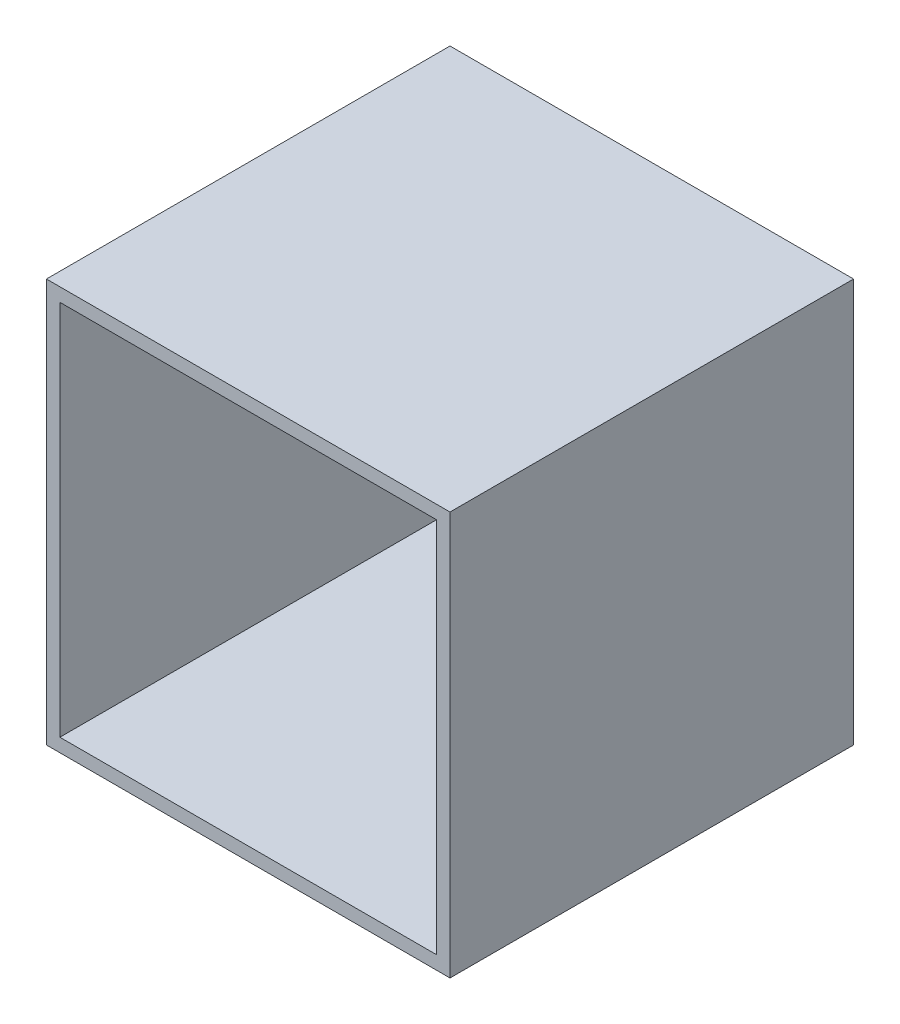
SolidWorks part; units mm, degrees
ref_plane "Front Plane" through (0, 0, 0) normal (0, 0, 1) x (1, 0, 0)
ref_plane "Top Plane" through (0, 0, 0) normal (0, 1, 0) x (1, 0, 0)
ref_plane "Right Plane" through (0, 0, 0) normal (1, 0, 0) x (0, 0, -1)
sketch "Sketch1" plane through (0, 0, 0) normal (0, 1, 0) x (1, 0, 0)
  line L1 (-38.1, -38.1) -> (38.1, -38.1)
  line L2 (-38.1, -38.1) -> (-38.1, 38.1)
  line L3 (-38.1, 38.1) -> (38.1, 38.1)
  line L4 (38.1, -38.1) -> (38.1, 38.1)
  line L5 (-38.1, -38.1) -> (38.1, 38.1) construction
  line L6 (-38.1, 38.1) -> (38.1, -38.1) construction
  point P0 (0, 0)
  dimension "D1" = 76.2
  dimension "D2" = 76.2
extrude "box" add sketch "Sketch1" along normal blind 76.2
shell "hollow it" thickness 2.54 removed face at (0, 38.1, 38.1)
sketch "Sketch2" plane through (0, 0, -38.1) normal (0, 0, -1) x (-1, 0, 0)
  line L0 (-38.1, 76.2) -> (38.1, 76.2) construction
  line L1 (-31.75, 69.85) -> (-24.13, 69.85)
  line L2 (-31.75, 69.85) -> (-31.75, 6.35)
  line L3 (-31.75, 6.35) -> (-24.13, 6.35)
  line L4 (-24.13, 69.85) -> (-24.13, 6.35)
  line L6 (-38.1, 76.2) -> (-38.1, 0) construction
  dimension "D1" = 7.62
  dimension "D2" = 63.5
  dimension "D3" = 6.35
  dimension "D4" = 6.35
extrude "slider track" cut sketch "Sketch2" against normal up to surface (2.54 mm away) up to face at (0, 38.1, -35.56)
sketch "Sketch4" plane through (0, 0, -38.1) normal (0, 0, -1) x (-1, 0, 0)
  line L0 (-38.1, 76.2) -> (38.1, 76.2) construction
  circle A0 centre (0, 63.5) radius 6.35
  dimension "D1" = 12.7
  dimension "D2" = 12.7
extrude "button large ring" cut sketch "Sketch4" against normal blind 1.27
sketch "Sketch5" plane through (0, 0, -36.83) normal (0, 0, -1) x (-1, 0, 0)
  circle A0 centre (0, 63.5) radius 3.556
  circle A1 centre (0, 63.5) radius 6.35 construction
  dimension "D2" = 7.112
  dimension "D1" = 0
extrude "button small hole" cut sketch "Sketch5" against normal blind 1.27
sketch "Sketch6" plane through (0, 0, -38.1) normal (0, 0, -1) x (-1, 0, 0)
  line L0 (-3.2977, 45.72) -> (-3.2977, 52.07)
  line L1 (-3.2977, 52.07) -> (3.0523, 52.07)
  line L2 (3.0523, 52.07) -> (3.0523, 45.72)
  line L3 (3.0523, 45.72) -> (9.4023, 45.72)
  line L4 (9.4023, 45.72) -> (9.4023, 39.37)
  line L5 (9.4023, 39.37) -> (3.0523, 39.37)
  line L6 (3.0523, 39.37) -> (3.0523, 33.02)
  line L7 (3.0523, 33.02) -> (-3.2977, 33.02)
  line L8 (-3.2977, 33.02) -> (-3.2977, 39.37)
  line L9 (-3.2977, 39.37) -> (-9.6477, 39.37)
  line L10 (-9.6477, 39.37) -> (-9.6477, 45.72)
  line L11 (-9.6477, 45.72) -> (-3.2977, 45.72)
  line L12 (-38.1, 0) -> (38.1, 0) construction
  dimension "D1" = 6.35
  dimension "D2" = 6.35
  dimension "D3" = 6.35
  dimension "D4" = 6.35
  dimension "D5" = 6.35
  dimension "D6" = 6.35
  dimension "D7" = 6.35
  dimension "D8" = 6.35
  dimension "D9" = 6.35
  dimension "D10" = 33.02
extrude "dpad large shape" cut sketch "Sketch6" against normal blind 1.27
sketch "Sketch7" plane through (0, 0, -36.83) normal (0, 0, -1) x (-1, 0, 0)
  line L0 (-3.2977, 45.72) -> (-9.6477, 45.72) construction
  line L1 (-9.6477, 45.72) -> (-9.6477, 39.37) construction
  line L2 (3.0523, 33.02) -> (3.0523, 39.37) construction
  line L3 (-3.2977, 33.02) -> (3.0523, 33.02) construction
  line L4 (3.0523, 39.37) -> (9.4023, 39.37) construction
  line L5 (9.4023, 39.37) -> (9.4023, 45.72) construction
  line L6 (3.0523, 45.72) -> (3.0523, 52.07) construction
  line L7 (-3.2977, 52.07) -> (-3.2977, 45.72) construction
  line L8 (3.0523, 52.07) -> (-3.2977, 52.07) construction
  circle A0 centre (-0.1227, 48.895) radius 1.905
  circle A1 centre (6.2273, 42.672) radius 1.905
  circle A2 centre (-0.1227, 36.195) radius 1.905
  circle A3 centre (-6.4727, 42.545) radius 1.905
  point P12 (3.0523, 36.195)
  point P17 (6.2273, 39.37)
  dimension "D3" = 3.81
  dimension "D6" = 3.81
  dimension "D9" = 3.81
  dimension "D13" = 3.81
  dimension "D1" = 3.175
  dimension "D2" = 3.175
  dimension "D4" = 3.175
  dimension "D5" = 3.175
  dimension "D7" = 3.302
  dimension "D8" = 3.175
  dimension "D10" = 3.175
  dimension "D11" = 3.175
  dimension "D12" = 3.175
extrude "dpad tiny holes" cut sketch "Sketch7" against normal blind 1.27
sketch "Sketch8" plane through (0, 0, -38.1) normal (0, 0, -1) x (-1, 0, 0)
  line L0 (38.1, 76.2) -> (38.1, 0) construction
  line L1 (-38.1, 76.2) -> (38.1, 76.2) construction
  circle A0 centre (20.32, 19.05) radius 12.7
  dimension "D1" = 25.4
  dimension "D2" = 17.78
  dimension "D3" = 57.15
extrude "dial large ring" cut sketch "Sketch8" against normal blind 1.27
ref_point "dial center"
sketch "Sketch9" plane through (0, 0, -36.83) normal (0, 0, -1) x (-1, 0, 0)
  circle A0 centre (20.32, 19.05) radius 5.08
  dimension "D1" = 10.16
extrude "dial small hole" cut sketch "Sketch9" against normal blind 1.27
sketch "Sketch10" plane through (0, 73.66, 0) normal (0, -1, 0) x (1, 0, 0)
  line L0 (35.56, -35.56) -> (-35.56, -35.56) construction
  line L1 (-35.56, -35.56) -> (-35.56, 38.1) construction
  circle A0 centre (-12.7, -13.563) radius 3.81
  point P2 (0, -35.56)
  dimension "D1" = 25.4
  dimension "D2" = 22.86
extrude "obstruction for baton" add sketch "Sketch10" along normal blind 12.7
sketch "Sketch12" plane through (0, 0, -38.1) normal (0, 0, -1) x (-1, 0, 0)
  line L0 (38.1, 76.2) -> (38.1, 0) construction
  line L1 (-11.43, 30.48) -> (-2.54, 30.48)
  line L2 (-11.43, 30.48) -> (-11.43, 5.08)
  line L3 (-11.43, 5.08) -> (-2.54, 5.08)
  line L4 (-2.54, 30.48) -> (-2.54, 5.08)
  line L5 (-38.1, 0) -> (38.1, 0) construction
  dimension "D1" = 25.4
  dimension "D2" = 8.89
  dimension "D3" = 40.64
  dimension "D4" = 5.08
extrude "hole for scroll wheel" cut sketch "Sketch12" against normal blind 2.54
sketch "Sketch14" plane through (2.54, 0, 0) normal (1, 0, 0) x (0, 0, -1)
  line L0 (38.1, 5.08) -> (38.1, 30.48) construction
  circle A0 centre (38.1, 17.78) radius 6.35
extrude "nibble base 1" add sketch "Sketch14" against normal blind 5.08
sketch "Sketch15" plane through (11.43, 0, 0) normal (-1, 0, 0) x (0, 0, 1)
  line L0 (-38.1, 30.48) -> (-38.1, 5.08) construction
  circle A0 centre (-38.1, 17.78) radius 6.35
extrude "nibble base 2" add sketch "Sketch15" against normal blind 5.08
sketch "Sketch16" plane through (11.43, 0, 0) normal (-1, 0, 0) x (0, 0, 1)
  circle A0 centre (-38.1, 17.78) radius 3.302
extrude "nibble holes" cut sketch "Sketch16" against normal up to surface and the other way up to surface up to face at (16.51, 17.78, -41.275) other way up to face at (-2.54, 17.78, -41.275)
